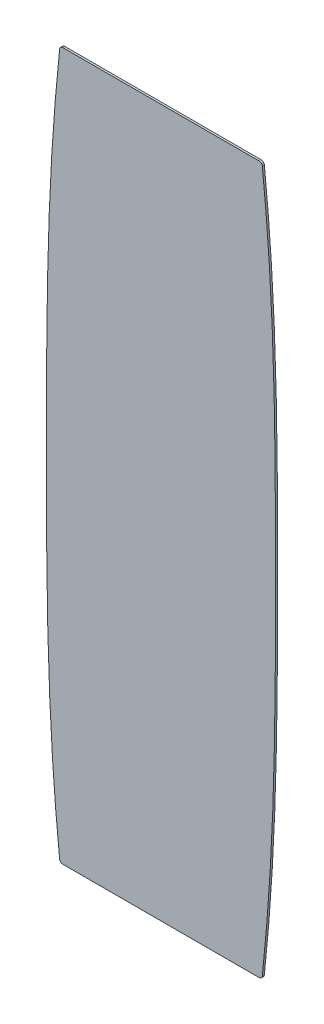
SolidWorks part; units mm, degrees
ref_plane "Front" through (0, 0, 0) normal (0, 0, 1) x (1, 0, 0)
ref_plane "Top" through (0, 0, 0) normal (0, 1, 0) x (1, 0, 0)
ref_plane "Right" through (0, 0, 0) normal (1, 0, 0) x (0, 0, -1)
sketch "Sketch1" plane through (0, 0, 0) normal (0, 0, 1) x (1, 0, 0)
  line L4 (-23.7959, -85.8) -> (23.7959, -85.8)
  line L5 (23.7959, 85.8) -> (-23.7959, 85.8)
  line L6 (-23.7959, -85.8) -> (23.7959, -85.8)
  line L7 (23.7959, 85.8) -> (-23.7959, 85.8)
  arc A8 (-24.5914, -85.0845) -> (-23.7959, -85.8) centre (-23.7959, -85) ccw
  arc A9 (23.7959, -85.8) -> (24.5914, -85.0845) centre (23.7959, -85) ccw
  arc A10 (24.5914, 85.0845) -> (23.7959, 85.8) centre (23.7959, 85) ccw
  arc A11 (-23.7959, 85.8) -> (-24.5914, 85.0845) centre (-23.7959, 85) ccw
  arc A12 (-24.5914, -85.0845) -> (-23.7959, -85.8) centre (-23.7959, -85) ccw
  arc A13 (23.7959, -85.8) -> (24.5914, -85.0845) centre (23.7959, -85) ccw
  arc A14 (24.5914, 85.0845) -> (23.7959, 85.8) centre (23.7959, 85) ccw
  arc A15 (-23.7959, 85.8) -> (-24.5914, 85.0845) centre (-23.7959, 85) ccw
  spline S8 degree 3 poles (-2806.4918, 894.8022) (60.8058, 596.2666) (-30.4322, 287.3177) (-27.6629, -28.4006) (-27.5516, -35.4997) (-27.1348, -49.6946) (-26.8273, -56.7856) (-26.1559, -67.4085) (-25.8975, -70.9473) (14.4616, -550.8183) (758.1325, -981.5501) (2605.5859, -1340.7425) knots -10.616772 -10.616772 -10.616772 -10.616772 0.25 0.25 0.5 0.5 0.75 0.75 0.875 0.875 17.712809 17.712809 17.712809 17.712809 only from (-27.8, 0) to (-24.5914, -85.0845)
  spline S9 degree 3 poles (-2802.3211, -847.651) (-343.2046, -714.1728) (4.9464, -402.7861) (26.8287, -56.7783) (27.1351, -49.686) (27.5518, -35.4924) (27.663, -28.3946) (30.4332, 287.5438) (-60.9175, 597.3895) (2812.1272, 875.5412) knots -11.707589 -11.707589 -11.707589 -11.707589 0.25 0.25 0.5 0.5 0.75 0.75 11.627179 11.627179 11.627179 11.627179 only from (24.5914, -85.0845) to (27.8, 0)
  spline S10 degree 3 poles (2806.4918, -894.8022) (-60.8058, -596.2666) (30.4322, -287.3177) (27.6629, 28.4006) (27.5516, 35.4997) (27.1348, 49.6946) (26.8273, 56.7856) (26.1559, 67.4085) (25.8975, 70.9473) (-14.4616, 550.8183) (-758.1325, 981.5501) (-2605.5859, 1340.7425) knots -10.616772 -10.616772 -10.616772 -10.616772 0.25 0.25 0.5 0.5 0.75 0.75 0.875 0.875 17.712809 17.712809 17.712809 17.712809 only from (27.8, 0) to (24.5914, 85.0845)
  spline S11 degree 3 poles (2802.3211, 847.651) (343.2046, 714.1728) (-4.9464, 402.7861) (-26.8287, 56.7783) (-27.1351, 49.686) (-27.5518, 35.4924) (-27.663, 28.3946) (-30.4332, -287.5438) (60.9175, -597.3895) (-2812.1272, -875.5412) knots -11.707589 -11.707589 -11.707589 -11.707589 0.25 0.25 0.5 0.5 0.75 0.75 11.627179 11.627179 11.627179 11.627179 only from (-24.5914, 85.0845) to (-27.8, 0)
  spline S12 degree 3 poles (-27.8, 0) (-27.8, -7.1003) (-27.7874, -14.2005) (-27.6629, -28.4006) (-27.5516, -35.4997) (-27.1348, -49.6946) (-26.8273, -56.7856) (-26.1559, -67.4085) (-25.8975, -70.9473) (-25.3027, -78.0197) (-24.9665, -81.5533) (-24.5914, -85.0845) knots 0 0 0 0 0.25 0.25 0.5 0.5 0.75 0.75 0.875 0.875 1 1 1 1
  spline S13 degree 3 poles (24.5914, -85.0845) (25.3415, -78.024) (25.9324, -70.9502) (26.8287, -56.7783) (27.1351, -49.686) (27.5518, -35.4924) (27.663, -28.3946) (27.7874, -14.1979) (27.8, -7.099) (27.8, 0) knots 0 0 0 0 0.25 0.25 0.5 0.5 0.75 0.75 1 1 1 1
  spline S14 degree 3 poles (27.8, 0) (27.8, 7.1003) (27.7874, 14.2005) (27.6629, 28.4006) (27.5516, 35.4997) (27.1348, 49.6946) (26.8273, 56.7856) (26.1559, 67.4085) (25.8975, 70.9473) (25.3027, 78.0197) (24.9665, 81.5533) (24.5914, 85.0845) knots 0 0 0 0 0.25 0.25 0.5 0.5 0.75 0.75 0.875 0.875 1 1 1 1
  spline S15 degree 3 poles (-24.5914, 85.0845) (-25.3415, 78.024) (-25.9324, 70.9502) (-26.8287, 56.7783) (-27.1351, 49.686) (-27.5518, 35.4924) (-27.663, 28.3946) (-27.7874, 14.1979) (-27.8, 7.099) (-27.8, 0) knots 0 0 0 0 0.25 0.25 0.5 0.5 0.75 0.75 1 1 1 1
  dimension "D1" = 0.2
extrude "Boss-Extrude1" add sketch "Sketch1" along normal up to surface (0.5 mm away)
